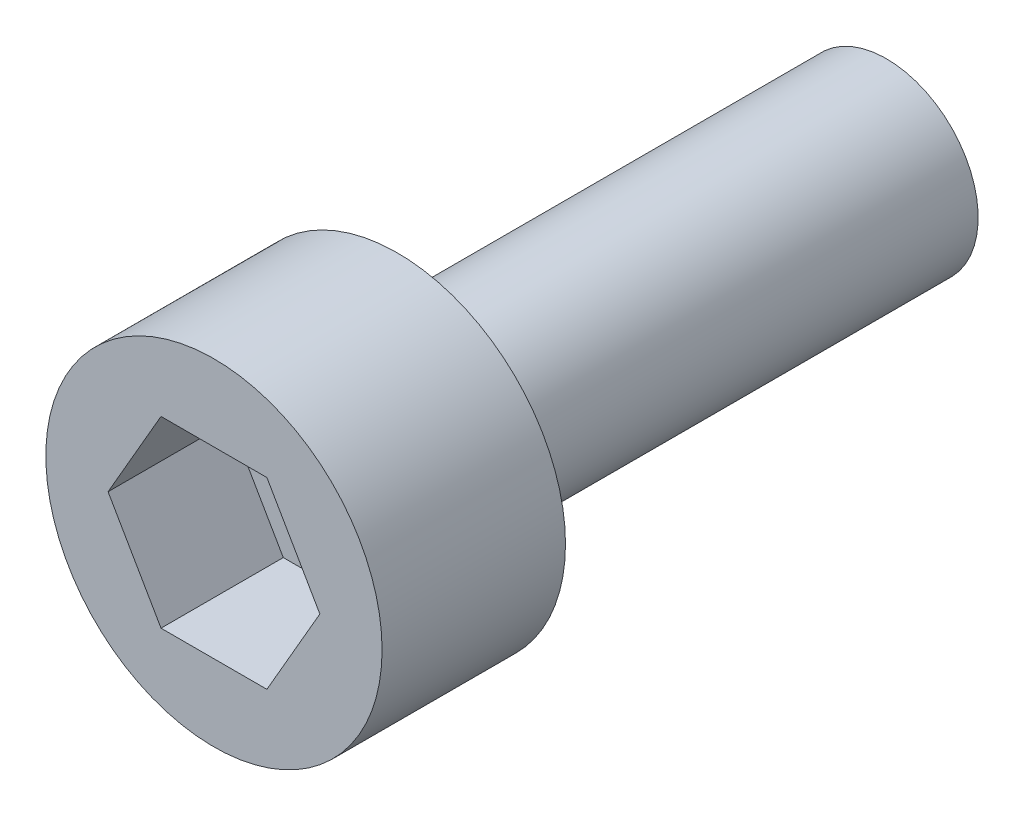
SolidWorks part; units mm, degrees
ref_plane "前视基准面" through (0, 0, 0) normal (0, 0, 1) x (1, 0, 0)
ref_plane "上视基准面" through (0, 0, 0) normal (0, 1, 0) x (1, 0, 0)
ref_plane "右视基准面" through (0, 0, 0) normal (1, 0, 0) x (0, 0, -1)
sketch "草图1" plane through (0, 0, 0) normal (0, 0, 1) x (1, 0, 0)
  line L1 (1.7321, 0) -> (0.866, 1.5)
  line L2 (0.866, 1.5) -> (-0.866, 1.5)
  line L3 (-0.866, 1.5) -> (-1.7321, 0)
  line L4 (-1.7321, 0) -> (-0.866, -1.5)
  line L5 (-0.866, -1.5) -> (0.866, -1.5)
  line L6 (0.866, -1.5) -> (1.7321, 0)
  circle A0 centre (0, 0) radius 2.75
  circle A1 centre (0, 0) radius 1.5 construction
  dimension "D1" = 5.5
  dimension "D2" = 3
extrude "凸台-拉伸1" add sketch "草图1" along normal blind 3
sketch "草图2" plane through (0, 0, 0) normal (0, 0, -1) x (-1, 0, 0)
  circle A0 centre (0, 0) radius 1.5
  dimension "D1" = 3
extrude "凸台-拉伸2" add sketch "草图2" along normal blind 8
cosmetic thread "装饰螺纹线1" parameters "D1"=8, "D2"=2
extrude "凸台-拉伸3" add sketch "草图1<3>" along normal blind 1 from surface contours L5 L6 L1 L2 L3 L4 region at (0, 0, 0) starting at face at (2.75, 0, 0)
sketch "草图1<3>" plane through (0, 0, 0) normal (0, 0, 1) x (1, 0, 0) same geometry as "草图1"
